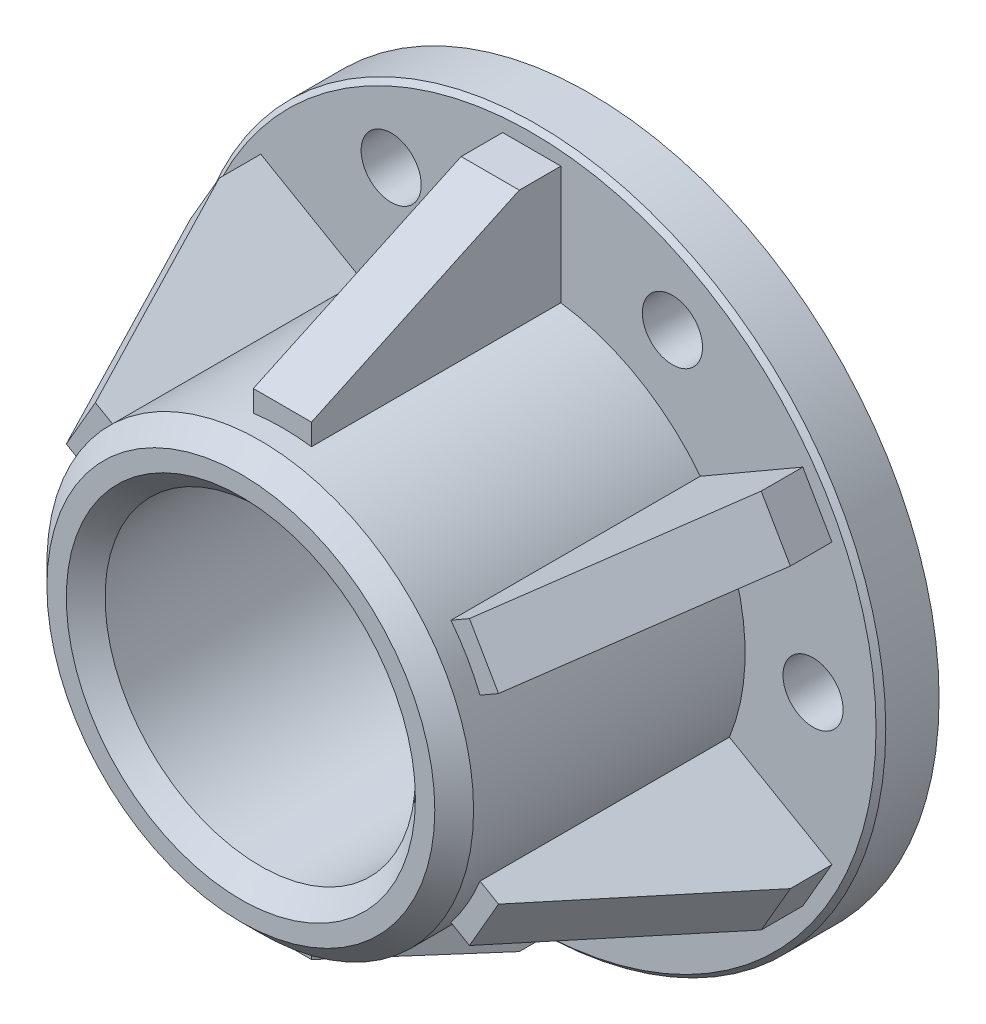
SolidWorks part; units mm, degrees
ref_plane "Front Plane" through (0, 0, 0) normal (0, 0, 1) x (1, 0, 0)
ref_plane "Top Plane" through (0, 0, 0) normal (0, 1, 0) x (1, 0, 0)
ref_plane "Right Plane" through (0, 0, 0) normal (1, 0, 0) x (0, 0, -1)
sketch "Sketch1" plane through (0, 0, 0) normal (0, 0, 1) x (1, 0, 0)
  line L0 (163, 28) -> (163, 50.8466) construction
  circle A0 centre (163, 28) radius 8 construction
  circle A2 centre (163, 28) radius 8
  circle A3 centre (163, 28) radius 18
  dimension "D1" = 10
extrude "Boss-Extrude1" add sketch "Sketch1" along normal blind 3
sketch "Sketch2" plane through (0, 0, 3) normal (0, 0, 1) x (1, 0, 0)
  line L0 (163, 28) -> (163, 36) construction
  circle A0 centre (163, 28) radius 11
  circle A1 centre (163, 28) radius 8 construction
  circle A2 centre (163, 28) radius 8
  dimension "D1" = 3
extrude "Boss-Extrude2" add sketch "Sketch2" along normal blind 15
ref_plane "Plane1" through (163, 0, 0) normal (1, 0, 0) x (0, 0, -1)
sketch "Sketch6" plane through (163, 0, 0) normal (1, 0, 0) x (0, 0, -1)
  line L0 (-18, 39) -> (-3, 46) construction
  line L1 (-15.8571, 40) -> (-5.1429, 45)
  line L2 (-3, 39) -> (-18, 39) construction
  line L3 (-3, 38.9) -> (-2.9, 38.9)
  line L4 (-15.8571, 40) -> (-15.8571, 39)
  line L5 (-15.8571, 39) -> (-15.8571, 38.9)
  line L6 (-15.8571, 38.9) -> (-3, 38.9)
  line L7 (-3, 45) -> (-5.1429, 45)
  line L8 (-2.9, 38.9) -> (-2.9, 45)
  line L9 (-2.9, 45) -> (-3, 45)
  dimension "D1" = 1
  dimension "D2" = 1
  dimension "D3" = 0.1
  dimension "D4" = 0.1
extrude "Boss-Extrude4" add sketch "Sketch6" along normal mid plane 3
pattern_circular "CirPattern1" count 6 over 360 about axis through (163, 28, 18) along (0, 0, 1) of "Boss-Extrude4"
sketch "Sketch7" plane through (0, 0, 3) normal (0, 0, 1) x (1, 0, 0)
  line L3 (168.5, 37.5263) -> (172, 43.5885) construction
  circle A1 centre (163, 28) radius 18 construction
  circle A2 centre (163, 28) radius 11 construction
  circle A3 centre (163, 28) radius 11
  point P5 (170.25, 40.5574)
  point P12 (177.5, 28)
  point P13 (170.25, 15.4426)
  point P14 (155.75, 15.4426)
  point P15 (148.5, 28)
  point P16 (155.75, 40.5574)
  point P17 (163, 28)
  dimension "D1" = 6
hole_wizard "M (0.295) Diameter Hole1" positions "Sketch10" profile "Sketch9" hole size "M" standard "ANSI Inch" end condition through all
sketch "Sketch10" plane through (0, 0, 3) normal (0, 0, 1) x (1, 0, 0)
  point P0 (155.75, 40.5574)
  point P3 (170.25, 40.5574)
  point P6 (177.5, 28)
  point P9 (170.25, 15.4426)
  point P12 (155.75, 15.4426)
  point P15 (148.5, 28)
sketch "Sketch9" plane through (155.75, 40.5574, 3) normal (1, 0, 0) x (0, -1, 0)
  line L0 (0, 0) -> (0, 3)
  line L1 (0, 3) -> (1.55, 3)
  line L2 (1.55, 3) -> (1.55, 0)
  line L5 (1.55, 0) -> (0, 0)
  line L11 (0, -6.35) -> (0, 107.95) construction
  dimension "Thru Hole Dia." = 3.1
  dimension "Thru Hole Depth" = 3
chamfer "Chamfer1" distance 1 angle 45 2 edges at (171, 28, 18) (174, 28, 18)
chamfer "Chamfer6" distance 0.25 angle 45 1 edges at (181, 28, 3)
